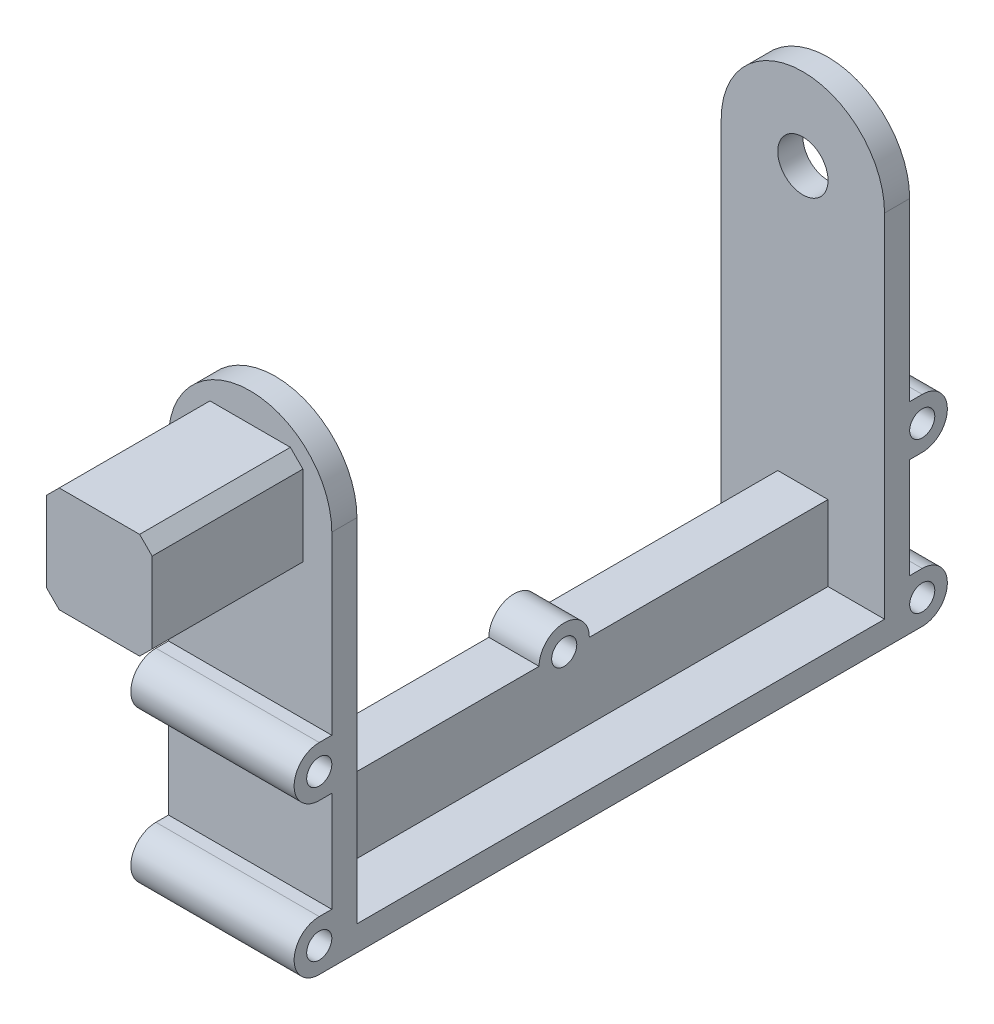
SolidWorks part; units mm, degrees
ref_plane "Front Plane" through (0, 0, 0) normal (0, 0, 1) x (1, 0, 0)
ref_plane "Top Plane" through (0, 0, 0) normal (0, 1, 0) x (1, 0, 0)
ref_plane "Right Plane" through (0, 0, 0) normal (1, 0, 0) x (0, 0, -1)
sketch "Sketch1" plane through (0, 0, 0) normal (0, 0, 1) x (1, 0, 0)
  line L1 (-32.5, 0) -> (32.5, 0)
  line L2 (-32.5, 0) -> (-32.5, -150)
  line L3 (-32.5, -150) -> (32.5, -150)
  line L4 (32.5, 0) -> (32.5, -150)
  circle A0 centre (0, 0) radius 32.5
  circle A1 centre (0, 0) radius 10
  dimension "D1" = 65
  dimension "D3" = 20
  dimension "D2" = 150
extrude "Boss-Extrude1" add sketch "Sketch1" along normal blind 10 contours A0 L2 L3 L4 | A1 L1 A0 | A1 L1 A0 region at (0, 14.792, 0) region at (0, -14.792, 0) region at (0, -87.5514, 0)
sketch "Sketch2" plane through (0, 0, 0) normal (0, 0, -1) x (-1, 0, 0)
  line L0 (-32.5, 0) -> (-32.5, -150) construction
  line L1 (32.5, -150) -> (-32.5, -150)
  line L2 (32.5, -150) -> (32.5, -140)
  line L3 (32.5, -140) -> (-32.5, -140)
  line L4 (-32.5, -150) -> (-32.5, -140)
  dimension "D1" = 10
extrude "Boss-Extrude2" add sketch "Sketch2" along normal blind 105
mirror "Mirror1" about plane through (0, 0, -105) normal (0, 0, -1) of bodies 102
sketch "Sketch3" plane through (0, 0, 10) normal (0, 0, 1) x (1, 0, 0)
  line L1 (21, -21) -> (-21, -21)
  line L2 (21, -21) -> (21, 21)
  line L3 (21, 21) -> (-21, 21)
  line L4 (-21, -21) -> (-21, 21)
  line L5 (21, -21) -> (-21, 21) construction
  line L6 (21, 21) -> (-21, -21) construction
  point P0 (0, 0)
  dimension "D1" = 42
extrude "Boss-Extrude3" add sketch "Sketch3" along normal blind 60
chamfer "Chamfer1" distance 5 angle 45 4 edges at (-21, -21, 40) (21, -21, 40) (21, 21, 40) (-21, 21, 40)
sketch "Sketch4" plane through (32.5, 0, 0) normal (1, 0, 0) x (0, 0, -1)
  line L1 (-10, 0) -> (-10, -150) construction
  line L3 (220, 0) -> (220, -150) construction
  line L5 (-15, -70) -> (-10, -70)
  line L6 (-15, -70) -> (-15, -90) construction
  line L7 (-15, -90) -> (-10, -90)
  line L8 (-10, -70) -> (-10, -90)
  line L9 (-15, -130) -> (-10, -130)
  line L10 (-15, -130) -> (-15, -150) construction
  line L11 (-15, -150) -> (-10, -150)
  line L12 (-10, -130) -> (-10, -150)
  line L13 (225, -70) -> (220, -70)
  line L14 (225, -70) -> (225, -90) construction
  line L15 (225, -90) -> (220, -90)
  line L16 (220, -70) -> (220, -90)
  line L17 (225, -130) -> (220, -130)
  line L18 (225, -130) -> (225, -150) construction
  line L19 (225, -150) -> (220, -150)
  line L20 (220, -130) -> (220, -150)
  circle A0 centre (-15, -80) radius 5
  circle A1 centre (-15, -140) radius 5
  circle A2 centre (225, -80) radius 5
  circle A3 centre (225, -140) radius 5
  arc A4 (-15, -70) -> (-15, -90) centre (-15, -80) ccw
  arc A5 (-15, -130) -> (-15, -150) centre (-15, -140) ccw
  arc A6 (220, -71.3397) -> (220, -88.6603) centre (225, -80) ccw
  arc A7 (220, -131.3397) -> (220, -148.6603) centre (225, -140) ccw
  arc A8 (-10, -148.6603) -> (-10, -131.3397) centre (-15, -140) ccw
  arc A9 (-10, -88.6603) -> (-10, -71.3397) centre (-15, -80) ccw
  arc A10 (225, -90) -> (225, -70) centre (225, -80) ccw
  arc A11 (225, -150) -> (225, -130) centre (225, -140) ccw
  line M22 (-10, 0) -> (-10, -150)
  line M24 (220, -150) -> (220, 0)
  dimension "D1" = 10
  dimension "D3" = 5
  dimension "D2" = 60
extrude "Boss-Extrude6" add sketch "Sketch4" against normal up to surface (65 mm away) contours L5 A4 L7 L8 A0 M22 | L8 A9 | L9 A5 L11 L12 A1 M22 | L12 A8 | L15 A10 L13 L16 A2 M24 | L16 A6 | L19 A11 L17 L20 A3 M24 | L20 A7 region at (32.5, -130.6699, 10.25) region at (32.5, -70.25, 12.5) region at (32.5, -80, 7.9498) region at (32.5, -140, 7.9498) region at (32.5, -80, -234.75) region at (32.5, -130.25, -222.5) region at (32.5, -80, -217.9498) region at (32.5, -140, -217.9498) up to face at (-32.5, -72.5, -105)
sketch "Sketch5" plane through (0, 0, 0) normal (1, 0, 0) x (0, 0, -1)
  line L0 (-15, -80) -> (-15, -140) construction
  line L1 (-15, -110) -> (225, -110) construction
  line L2 (95, -110) -> (0, -110)
  line L3 (225, -80) -> (225, -140) construction
  line L4 (0, 0) -> (0, -140) construction
  line L5 (0, -110) -> (0, -140)
  line L6 (210, -140) -> (0, -140) construction
  line L7 (0, -140) -> (210, -140)
  line L8 (210, -140) -> (210, -110)
  line L9 (210, 0) -> (210, -140) construction
  line L10 (210, -110) -> (115, -110)
  circle A0 centre (105, -110) radius 5
  arc A1 (115, -110) -> (95, -110) centre (105, -110) ccw
  point P13 (105, -110)
  dimension "D1" = 10
  dimension "D2" = 20
extrude "Boss-Extrude9" add sketch "Sketch5" along normal blind 10 and the other way blind 10
